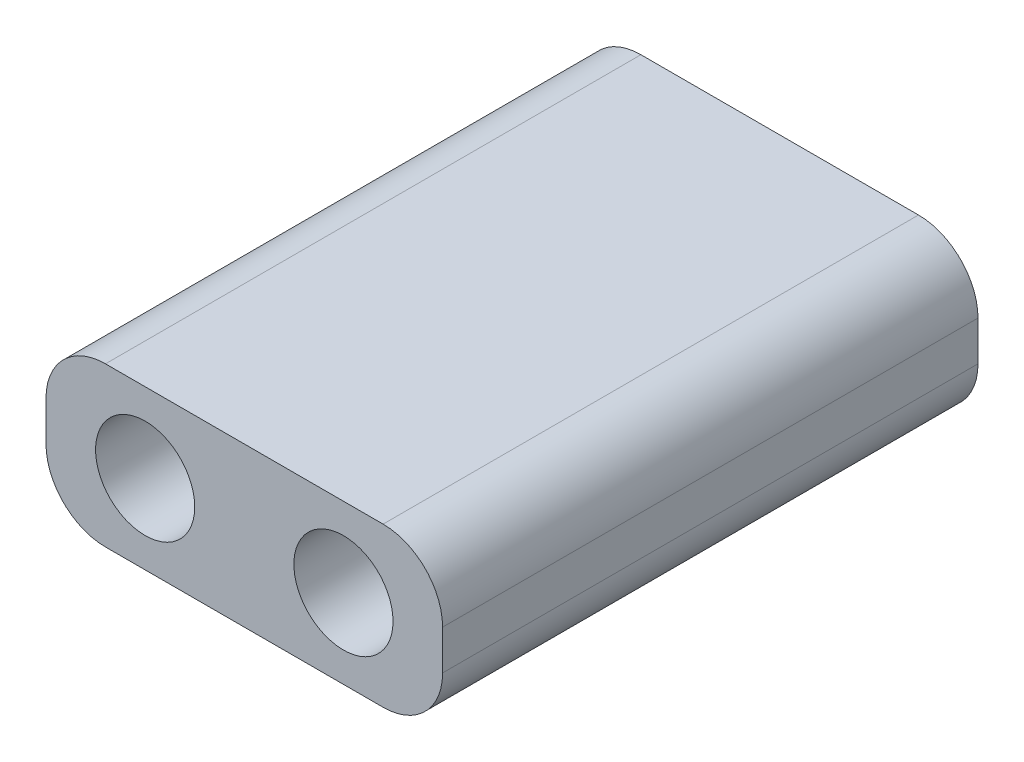
SolidWorks part; units mm, degrees
ref_plane "Front Plane" through (0, 0, 0) normal (0, 0, 1) x (1, 0, 0)
ref_plane "Top Plane" through (0, 0, 0) normal (0, 1, 0) x (1, 0, 0)
ref_plane "Right Plane" through (0, 0, 0) normal (1, 0, 0) x (0, 0, -1)
sketch "Sketch2" plane through (0, 0, 0) normal (0, 0, 1) x (1, 0, 0)
  line L1 (-10, -4) -> (10, -4)
  line L2 (-10, -4) -> (-10, 4)
  line L3 (-10, 4) -> (10, 4)
  line L4 (10, -4) -> (10, 4)
  line L5 (-10, -4) -> (10, 4) construction
  line L6 (-10, 4) -> (10, -4) construction
  point P0 (0, 0)
  dimension "D1" = 8
  dimension "D2" = 20
extrude "Boss-Extrude1" add sketch "Sketch2" along normal blind 27
sketch "Sketch3" plane through (0, 0, 27) normal (0, 0, 1) x (1, 0, 0)
  line L0 (0, 0) -> (-5, 0)
  line L1 (0, 0) -> (5, 0)
  circle A0 centre (-5, 0) radius 2.5
  circle A1 centre (5, 0) radius 2.5
  dimension "D2" = 5
  dimension "D4" = 5
  dimension "D1" = 5
  dimension "D3" = 5
extrude "Cut-Extrude1" cut sketch "Sketch3" against normal blind 34 contours A0 | A1 region at (-7.4293, 0, 27) region at (5, 2.4293, 27)
fillet "Fillet1" radius 3 4 edges at (10, -4, 13.5) (10, 4, 13.5) (-10, -4, 13.5) (-10, 4, 13.5)
